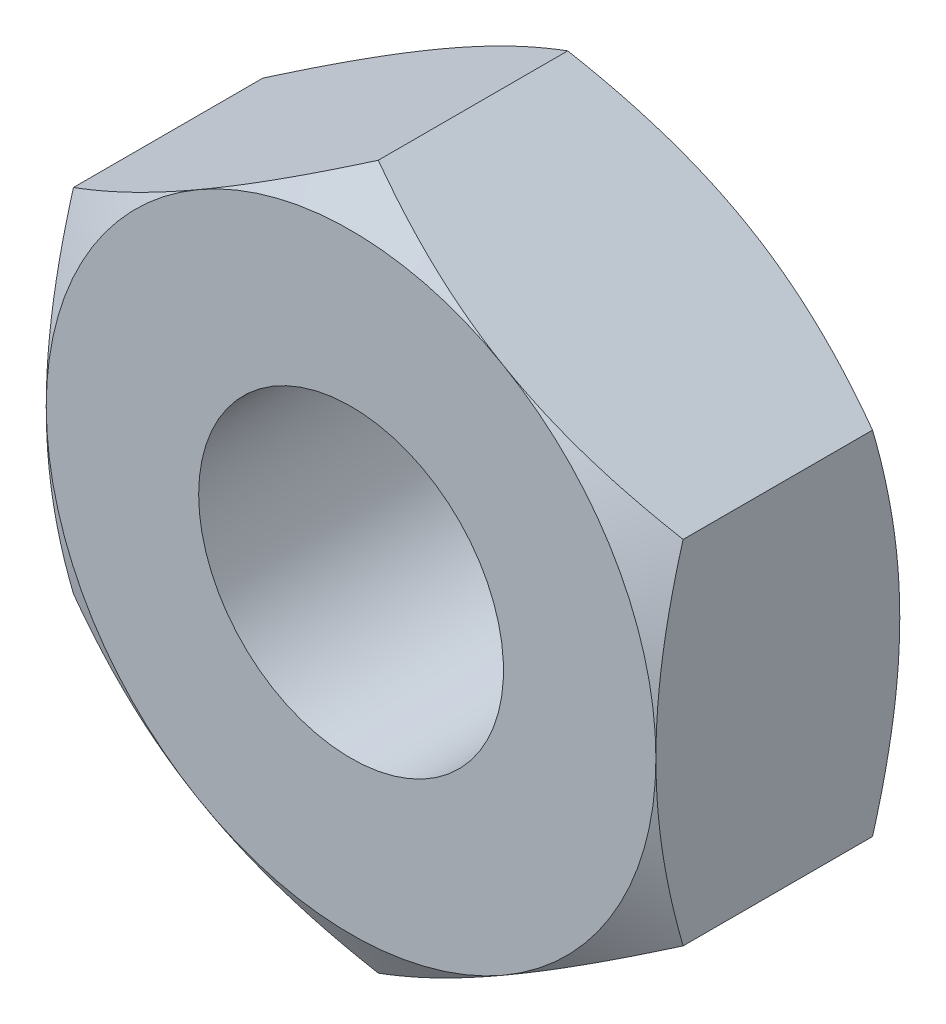
SolidWorks part; units mm, degrees
ref_plane "Front" through (0, 0, 0) normal (0, 0, 1) x (1, 0, 0)
ref_plane "Top" through (0, 0, 0) normal (0, 1, 0) x (1, 0, 0)
ref_plane "Right" through (0, 0, 0) normal (1, 0, 0) x (0, 0, -1)
sketch "Sketch1" plane through (0, 0, 0) normal (0, 0, 1) x (1, 0, 0)
  line L1 (-2.5, 1.4434) -> (-2.5, -1.4434)
  line L2 (-2.5, -1.4434) -> (0, -2.8868)
  line L3 (0, -2.8868) -> (2.5, -1.4434)
  line L4 (2.5, -1.4434) -> (2.5, 1.4434)
  line L5 (2.5, 1.4434) -> (0, 2.8868)
  line L6 (0, 2.8868) -> (-2.5, 1.4434)
  circle A0 centre (0, 0) radius 2.5 construction
  circle A1 centre (0, 0) radius 1.25 construction
  point P10 (0, 1.25)
  dimension "hex" = 5
  dimension "dia" = 2.5
extrude "Extrude1" add sketch "Sketch1" along normal mid plane 2
sketch "Sketch4" plane through (0, 0, -1) normal (0, 0, -1) x (-1, 0, 0)
  circle A0 centre (0, 0) radius 1.25 construction
  circle A1 centre (0, 0) radius 1.25
sketch "Sketch10" plane through (0, 0, 1) normal (0, 0, 1) x (1, 0, 0)
  circle A0 centre (0, 0) radius 1.25 construction
  circle A1 centre (0, 0) radius 1.25
extrude "Cut-Extrude2" cut sketch "Sketch10" against normal through all draft 45
sketch "Sketch11" plane through (0, 0, -1) normal (0, 0, -1) x (-1, 0, 0)
  circle A0 centre (0, 0) radius 1.25 construction
  circle A1 centre (0, 0) radius 1.25
extrude "Cut-Extrude3" cut sketch "Sketch11" against normal through all draft 45
sketch "Sketch13" plane through (0, 0, -1) normal (0, 0, -1) x (-1, 0, 0)
  circle A0 centre (0, 0) radius 1.25 construction
  circle A1 centre (0, 0) radius 1.25
extrude "Boss-Extrude1" add sketch "Sketch13" against normal up to vertex (2 mm away) separate body up to point (-2.5, 1.4434, 1)
curve "Helix/Spiral3" [suppressed] pitch 0.45 height 2 turns 4.4444
sketch "Sketch12" plane through (0, 0, 0) normal (1, 0, 0) x (0, 0, -1)
  line L0 (1.3938, 1.25) -> (1, 1.25)
  line L1 (1.3938, 1.25) -> (1.225, 0.9577)
  line L2 (1.225, 0.9577) -> (1.1688, 0.9577)
  line L3 (1.1688, 0.9577) -> (1, 1.25)
  line L4 (1.1969, 0.9577) -> (1.1969, 1.25) construction
  line L5 (1.0844, 1.1039) -> (1.3094, 1.1039) construction
  dimension "D1" = 60
  dimension "D2" = 0.0563
  dimension "D3" = 0.225
sweep "Cut-Sweep1" [suppressed] cut profiles "Sketch12" path "Helix/Spiral3"
combine bodies "Combine1" operation type subtract main body 116 bodies to subtract 117
sketch "Sketch7" plane through (0, 0, 1) normal (0, 0, 1) x (1, 0, 0)
  circle A0 centre (0, 0) radius 2.5 construction
  circle A1 centre (0, 0) radius 2.5
extrude "Extrude2" cut sketch "Sketch7" against normal blind 25.4 draft 60 flip side to cut
mirror "Mirror2" about plane through (0, 0, 0) normal (0, 0, 1) of "Extrude2"
sketch "Sketch8" plane through (0, 0, 1) normal (0, 0, 1) x (1, 0, 0)
  line L0 (-0.8839, 0.8839) -> (0, 0) construction
  line L1 (0, -1.2361) -> (0, 1.2361) construction
  circle A1 centre (0, 0) radius 1.25 construction
  point P0 (-0.8839, 0.8839)
  dimension "D1" = 45
sketch "Sketch14" plane through (0, 0, 1) normal (0, 0, 1) x (1, 0, 0)
  line L0 (0, 0) -> (-1.25, 0) construction
  circle A0 centre (0, 0) radius 1.25 construction
equation "\"D3@Helix/Spiral3\" = \"length@Extrude1\" "
equation "\"D2@Sketch12\" = \"D4@Helix/Spiral3\"*.125"
equation "\"D3@Sketch12\" = \"D4@Helix/Spiral3\"*.50"
